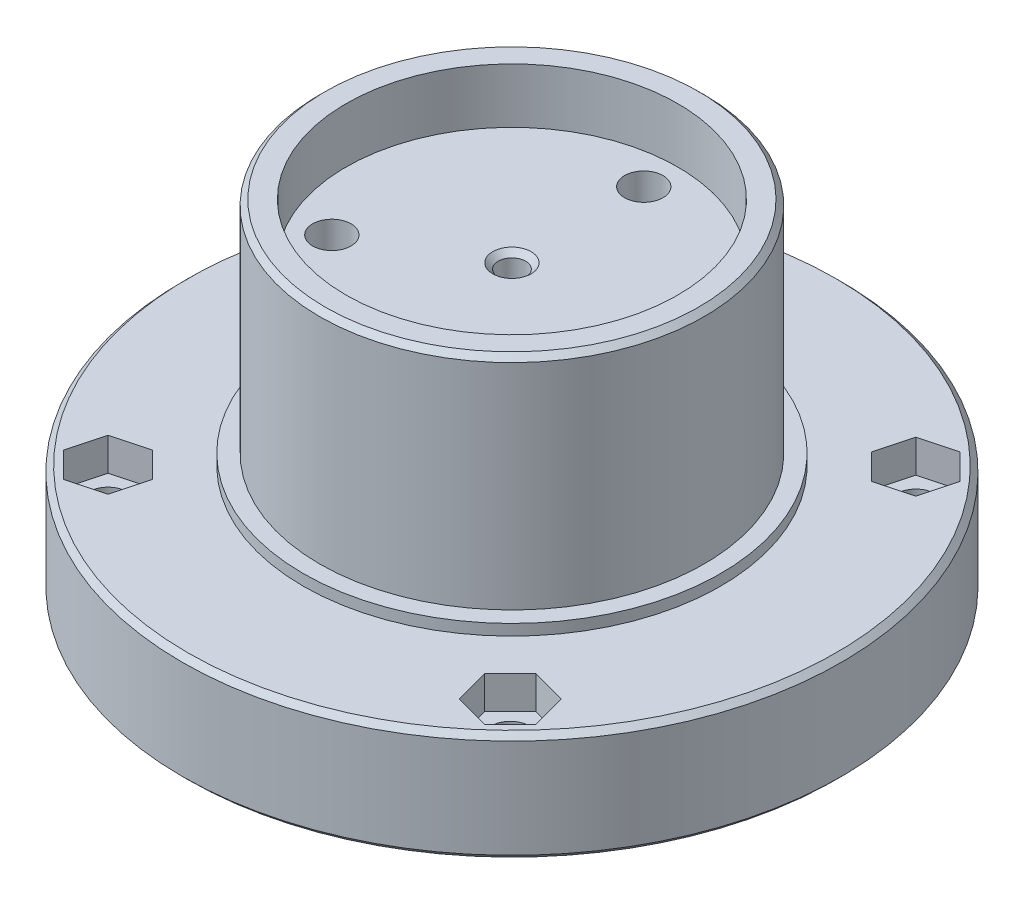
SolidWorks part; units mm, degrees
ref_plane "Front" through (0, 0, 0) normal (0, 0, 1) x (1, 0, 0)
ref_plane "Top" through (0, 0, 0) normal (0, 1, 0) x (1, 0, 0)
ref_plane "Right" through (0, 0, 0) normal (1, 0, 0) x (0, 0, -1)
sketch "Эскиз1" plane through (0, 0, 0) normal (0, 1, 0) x (1, 0, 0)
  circle A0 centre (0, 0) radius 30
extrude "Бобышка-Вытянуть1" add sketch "Эскиз1" along normal blind 10
sketch "Эскиз3" plane through (0, 0, 0) normal (0, 1, 0) x (1, 0, 0)
  circle A0 centre (0, 0) radius 19
extrude "Бобышка-Вытянуть2" add sketch "Эскиз3" along normal blind 1 from offset 10
sketch "Эскиз4" plane through (0, 0, 0) normal (0, 1, 0) x (1, 0, 0)
  circle A0 centre (0, 0) radius 17.5
extrude "Бобышка-Вытянуть3" add sketch "Эскиз4" along normal blind 20 from offset 11
sketch "Эскиз5" plane through (0, 31, 0) normal (0, 1, 0) x (1, 0, 0)
  circle A0 centre (0, 0) radius 15.1
  dimension "D1" = 30.2
extrude "Вырез-Вытянуть1" cut sketch "Эскиз5" against normal blind 5
sketch "Эскиз6" plane through (0, 0, 0) normal (0, 1, 0) x (1, 0, 0)
  circle A0 centre (0, 0) radius 12 construction
  circle A1 centre (0, 12) radius 1.75
extrude "Вырез-Вытянуть2" cut sketch "Эскиз6" along normal through all
pattern_circular "Круговой массив1" count 3 over 360 about axis through (0, 31, 0) along (0, -1, 0) of "Вырез-Вытянуть2"
sketch "Sketch1" plane through (0, 0, 0) normal (0, -1, 0) x (1, 0, 0)
  circle A0 centre (-10.3923, 6) radius 3.25
  circle A1 centre (10.3923, 6) radius 3.25
  circle A2 centre (0, -12) radius 3.25
  point P10 (0, 0)
  dimension "D1" = 3
extrude "Cut-Extrude1" cut sketch "Sketch1" against normal blind 14
sketch "Эскиз7" plane through (0, 0, 0) normal (0, -1, 0) x (1, 0, 0)
  circle A0 centre (0, 0) radius 1.25
extrude "Вырез-Вытянуть3" cut sketch "Эскиз7" against normal through all both and the other way through all
sketch "Эскиз8" plane through (0, 0, 0) normal (0, 1, 0) x (1, 0, 0)
  line L0 (0, 0) -> (18.4591, 18.3101) construction
  line L2 (20.7861, 15.9831) -> (21.6379, 19.1619)
  line L3 (21.6379, 19.1619) -> (19.3109, 21.4889)
  line L4 (19.3109, 21.4889) -> (16.1321, 20.6371)
  line L5 (16.1321, 20.6371) -> (15.2804, 17.4584)
  line L6 (15.2804, 17.4584) -> (17.6074, 15.1314)
  line L7 (17.6074, 15.1314) -> (20.7861, 15.9831)
  circle A0 centre (0, 0) radius 26 construction
  circle A1 centre (18.4591, 18.3101) radius 1.75
  circle A2 centre (18.4591, 18.3101) radius 2.85 construction
  dimension "D1" = 5.7
  dimension "D2" = 3.5
  dimension "D3" = 52
extrude "Вырез-Вытянуть4" cut sketch "Эскиз8" along normal through all contours A1
extrude "Вырез-Вытянуть5" cut sketch "Эскиз8<3>" along normal blind 10 from offset 7 contours L5 L6 L7 L2 L3 L4
sketch "Эскиз8<3>" plane through (0, 0, 0) normal (0, 1, 0) x (1, 0, 0) same geometry as "Эскиз8"
pattern_circular "Круговой массив2" count 4 over 360 about axis through (0, 10, 0) along (0, -1, 0) of "Вырез-Вытянуть5", "Вырез-Вытянуть4"
chamfer "Chamfer2" distance 0.5 angle 45 2 edges at (0, 0, 30) (0, 10, 30)
chamfer "Chamfer1" distance 0.5 angle 45 3 edges at (0, 31, 17.5) (0, 0, 1.25) (0, 26, 1.25)
sketch "Эскиз9" plane through (0, 0, 0) normal (0, -1, 0) x (1, 0, 0)
  circle A1 centre (0, 0) radius 12
extrude "Вырез-Вытянуть6" cut sketch "Эскиз9" against normal blind 7
fillet "Скругление1" radius 1 13 edges at (3.2201, 3.5, -11.5599) (11.6212, 3.5, 2.9913) (-3.2201, 3.5, -11.5599) (-11.6212, 3.5, 2.9913) (-8.4011, 3.5, 8.5686) (8.4011, 3.5, 8.5686) (10.3923, 7, -6) (0, 7, -8.75) (-10.3923, 7, -6) (-7.5777, 7, 4.375) (0, 7, 12) (7.5777, 7, 4.375) (0, 7, -1.25)
fillet "Скругление2" radius 1 12 edges at (8.3932, 0, 8.825) (13.2069, 0, 7.625) (11.8393, 0, 2.8562) (10.3923, 0, -6) (3.4461, 0, -11.6812) (0, 0, -15.25) (-3.4461, 0, -11.6812) (-10.3923, 0, -6) (-11.8393, 0, 2.8562) (-13.2069, 0, 7.625) (-8.3932, 0, 8.825) (0, 0, 12)
